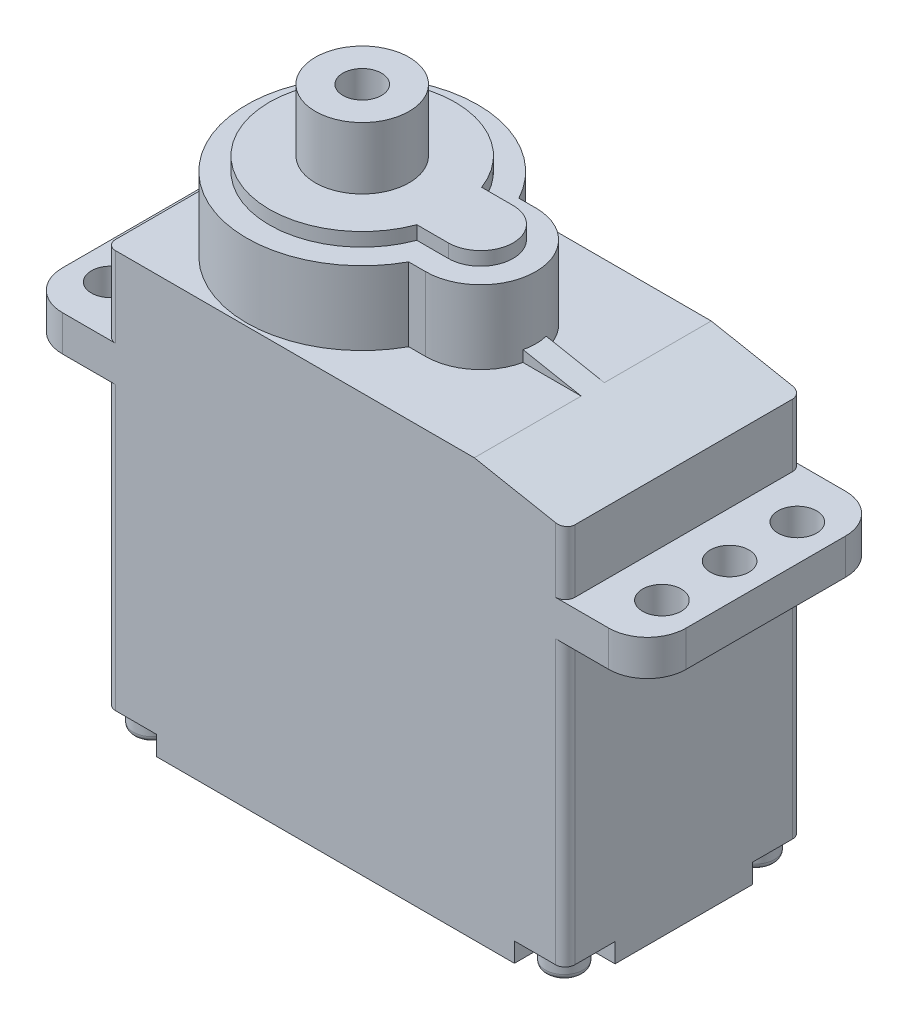
SolidWorks part; units mm, degrees
ref_plane "Front Plane" through (0, 0, 0) normal (0, 0, 1) x (1, 0, 0)
ref_plane "Top Plane" through (0, 0, 0) normal (0, 1, 0) x (1, 0, 0)
ref_plane "Right Plane" through (0, 0, 0) normal (1, 0, 0) x (0, 0, -1)
ref_axis "X-Axis" through (-88.99, 0, 0) along (1, 0, 0)
ref_axis "Y-Axis" through (0, 0, -88.99) along (0, 0, 1)
ref_axis "Z-Axis" through (0, 55, 0) along (0, -1, 0)
sketch "Sketch1" plane through (0, 0, 0) normal (0, 0, 1) x (1, 0, 0)
  line L0 (0, 0) -> (0, 13.7) construction
  line L1 (-7.13, 6) -> (11.92, 6)
  line L2 (-7.13, 6) -> (-7.13, 1.85)
  line L3 (-7.13, -15.6) -> (16.62, -15.6)
  line L4 (16.62, 5.1) -> (16.62, 1.85)
  line L5 (16.62, 1.85) -> (20.87, 1.85)
  line L6 (-11.38, 1.85) -> (-7.13, 1.85)
  line L7 (-11.38, 1.85) -> (-11.38, 0)
  line L8 (-11.38, 0) -> (-7.13, 0)
  line L9 (20.87, 1.85) -> (20.87, 0)
  line L10 (16.62, 0) -> (20.87, 0)
  line L11 (-7.13, 0) -> (-7.13, -15.6)
  line L12 (16.62, 0) -> (16.62, -15.6)
  line L13 (16.62, 5.1) -> (11.92, 6)
  line L14 (16.62, 0) -> (-7.13, 0) construction
  point P3 (4.745, 0)
  dimension "D1" = 1.85
  dimension "D2" = 32.25
  dimension "D3" = 23.75
  dimension "D4" = 15.6
  dimension "D5" = 21.6
  dimension "D6" = 7.13
  dimension "D7" = 16.62
  dimension "D8" = 0.9
  dimension "D9" = 4.7
  dimension "D10" = 29.3
  dimension "D11" = 4.745
extrude "Boss-Extrude1" add sketch "Sketch1" along normal mid plane 12.25
sketch "Sketch2" plane through (0, 6, 0) normal (0, 1, 0) x (1, 0, 0)
  line L0 (0, 0) -> (6.125, 0) construction
  line L1 (5.2515, -2.85) -> (6.125, -2.85)
  line L2 (6.125, 2.85) -> (5.2515, 2.85)
  line L3 (0, 0) -> (-5.975, 0) construction
  line L4 (6.125, 0) -> (8.975, 0) construction
  arc A0 (5.2515, 2.85) -> (5.2515, -2.85) centre (0, 0) ccw
  arc A1 (6.125, -2.85) -> (6.125, 2.85) centre (6.125, 0) ccw
  dimension "D1" = 11.95
  dimension "D2" = 5.7
  dimension "D3" = 14.95
extrude "Boss-Extrude2" add sketch "Sketch2" along normal blind 3.8
sketch "Sketch3" plane through (0, 9.8, 0) normal (0, 1, 0) x (1, 0, 0)
  line L0 (4.4983, -1.675) -> (6.125, -1.675)
  line L1 (6.125, 1.675) -> (4.4983, 1.675)
  line L2 (7.8, 0) -> (8.975, 0) construction
  line L3 (-4.8, 0) -> (-5.975, 0) construction
  arc A0 (4.4983, 1.675) -> (4.4983, -1.675) centre (0, 0) ccw
  arc A1 (6.125, -1.675) -> (6.125, 1.675) centre (6.125, 0) ccw
  arc A2 (6.125, -2.85) -> (6.125, 2.85) centre (6.125, 0) ccw construction
  arc A3 (5.2515, 2.85) -> (5.2515, -2.85) centre (0, 0) ccw construction
  dimension "D1" = 9.6
extrude "Boss-Extrude3" add sketch "Sketch3" along normal blind 0.7
sketch "Sketch4" plane through (0, 0, 0) normal (0, 1, 0) x (1, 0, 0)
  line L0 (-9.505, 0) -> (-7.13, 0) construction
  line L1 (-9.505, 3.5) -> (18.995, 3.5) construction
  line L2 (-9.505, 3.5) -> (-9.505, -3.5) construction
  line L3 (-9.505, -3.5) -> (18.995, -3.5) construction
  line L4 (18.995, 3.5) -> (18.995, -3.5) construction
  line L5 (18.995, 0) -> (16.62, 0) construction
  line L6 (-7.13, -6.125) -> (-7.13, 6.125) construction
  line L7 (16.62, -6.125) -> (16.62, 6.125) construction
  circle A0 centre (-9.505, 3.5) radius 1
  circle A1 centre (-9.505, -3.5) radius 1
  circle A2 centre (18.995, 3.5) radius 1
  circle A3 centre (18.995, -3.5) radius 1
  circle A4 centre (18.995, 0) radius 1
  circle A5 centre (-9.505, 0) radius 1
  dimension "D1" = 2
  dimension "D2" = 28.5
  dimension "D3" = 7
extrude "Cut-Extrude1" cut sketch "Sketch4" along normal through all
sketch "Sketch5" plane through (0, -15.6, 0) normal (0, -1, 0) x (1, 0, 0)
  line L0 (16.62, 6.125) -> (-7.13, -6.125) construction
  line L1 (16.62, 6.125) -> (13.995, 6.125)
  line L2 (16.62, 6.125) -> (16.62, 3.55)
  line L3 (16.62, 3.55) -> (15.295, 3.55)
  line L4 (13.995, 6.125) -> (13.995, 4.85)
  line L5 (16.62, -6.125) -> (13.995, -6.125)
  line L6 (16.62, -6.125) -> (16.62, -3.55)
  line L7 (16.62, -3.55) -> (15.295, -3.55)
  line L8 (13.995, -6.125) -> (13.995, -4.85)
  line L9 (-7.13, 6.125) -> (-4.505, 6.125)
  line L10 (-7.13, 6.125) -> (-7.13, 3.55)
  line L11 (-7.13, 3.55) -> (-5.805, 3.55)
  line L12 (-4.505, 6.125) -> (-4.505, 4.85)
  line L13 (-7.13, -6.125) -> (-4.505, -6.125)
  line L14 (-7.13, -6.125) -> (-7.13, -3.55)
  line L15 (-7.13, -3.55) -> (-5.805, -3.55)
  line L16 (-4.505, -6.125) -> (-4.505, -4.85)
  line L17 (-5.905, 4.95) -> (15.395, 4.95) construction
  line L18 (-5.905, 4.95) -> (-5.905, -4.95) construction
  line L19 (-5.905, -4.95) -> (15.395, -4.95) construction
  line L20 (15.395, 4.95) -> (15.395, -4.95) construction
  line L21 (-5.905, 4.95) -> (15.395, -4.95) construction
  arc A0 (13.995, -4.85) -> (15.295, -3.55) centre (15.295, -4.85) cw
  arc A1 (15.295, 3.55) -> (13.995, 4.85) centre (15.295, 4.85) cw
  arc A2 (-4.505, 4.85) -> (-5.805, 3.55) centre (-5.805, 4.85) cw
  arc A3 (-5.805, -3.55) -> (-4.505, -4.85) centre (-5.805, -4.85) cw
  circle A4 centre (-5.905, 4.95) radius 0.975
  circle A5 centre (-5.905, -4.95) radius 0.975
  circle A6 centre (15.395, -4.95) radius 0.975
  circle A7 centre (15.395, 4.95) radius 0.975
  point P36 (4.745, 0)
  dimension "D1" = 1.3
  dimension "D4" = 1.95
  dimension "D2" = 7.1
  dimension "D3" = 18.5
  dimension "D5" = 21.3
  dimension "D6" = 9.9
extrude "Cut-Extrude2" cut sketch "Sketch5" against normal blind 1
sketch "Sketch8" plane through (0, 0, 0) normal (0, 0, 1) x (1, 0, 0)
  line L0 (11.92, 6) -> (7.8, 6.7889)
  line L1 (7.8, 6.7889) -> (7.8, 6)
  line L2 (7.8, 6) -> (11.92, 6)
  line L3 (16.62, 5.1) -> (11.92, 6) construction
extrude "Boss-Extrude6" add sketch "Sketch8" along normal mid plane 1.2
sketch "Sketch9" plane through (0, 0, 0) normal (0, 0, 1) x (1, 0, 0)
  line L0 (1, 13.7) -> (2.425, 13.7)
  line L1 (2.425, 13.7) -> (2.425, 10.5)
  line L4 (2.425, 10.5) -> (1, 10.5)
  line L6 (1, 10.5) -> (1, 13.7)
  line L8 (4.4983, 10.5) -> (-4.8, 10.5) construction
  line L9 (0, 13.7) -> (0, 10.5) construction
  line L10 (0, 0) -> (0, 13.7) construction
  dimension "D1" = 2
  dimension "D4" = 4.85
revolve "Revolve1" add sketch "Sketch9" angle 360 about axis through (0, 55, 0) along (0, -1, 0)
fillet "Fillet1" radius 0.3 4 edges at (15.395, -15.6, -5.925) (15.395, -15.6, 3.975) (-5.905, -15.6, -5.925) (-5.905, -15.6, 3.975)
fillet "Fillet2" radius 2 4 edges at (20.87, 0.925, -6.125) (20.87, 0.925, 6.125) (-11.38, 0.925, 6.125) (-11.38, 0.925, -6.125)
fillet "Fillet3" radius 0.5 8 edges at (16.62, -7.3, -6.125) (16.62, 3.475, -6.125) (16.62, 3.475, 6.125) (16.62, -7.3, 6.125) (-7.13, -7.3, -6.125) (-7.13, 3.925, -6.125) (-7.13, 3.925, 6.125) (-7.13, -7.3, 6.125)
ref_axis "Axis1" through (-9.505, 1.85, 3.5) along (0, -1, 0)
ref_axis "Axis2" through (-9.505, 1.85, -3.5) along (0, -1, 0)
ref_axis "Axis3" through (18.995, 1.85, -3.5) along (0, -1, 0)
ref_axis "Axis4" through (18.995, 1.85, 3.5) along (0, -1, 0)
